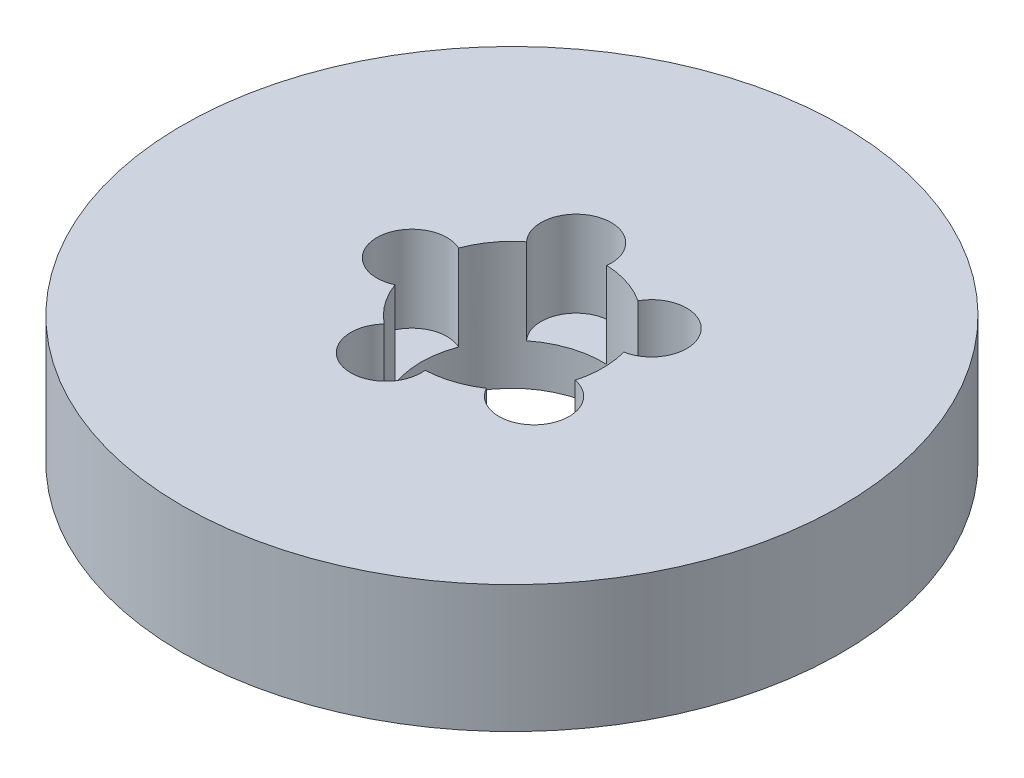
SolidWorks part; units mm, degrees
ref_plane "Front Plane" through (0, 0, 0) normal (0, 0, 1) x (1, 0, 0)
ref_plane "Top Plane" through (0, 0, 0) normal (0, 1, 0) x (1, 0, 0)
ref_plane "Right Plane" through (0, 0, 0) normal (1, 0, 0) x (0, 0, -1)
sketch "Sketch1" plane through (0, 0, 0) normal (0, 1, 0) x (1, 0, 0)
  circle A0 centre (0, 0) radius 72.5
  dimension "FLANGE_OD" = 145
extrude "Boss-Extrude1" add sketch "Sketch1" along normal blind 28
sketch "Sketch2" plane through (0, 0, 0) normal (0, 1, 0) x (1, 0, 0)
  circle A0 centre (0, 0) radius 20
  dimension "BORE_D" = 40
extrude "Cut-Extrude1" cut sketch "Sketch2" along normal through all
sketch "Sketch3" plane through (0, 28, 0) normal (0, 1, 0) x (1, 0, 0)
  circle A0 centre (0, 0) radius 21.9984 construction
  circle A1 centre (-21.9984, 0) radius 7.7248
  dimension "BOLT_D" = 15.4497
  dimension "BOLT_PCD" = 43.9968
extrude "Cut-Extrude2" cut sketch "Sketch3" against normal blind 18.8602
pattern_circular "CirPattern1" count 5 over 360 about axis through (0, 0, 0) along (0, 1, 0) of "Cut-Extrude2"
